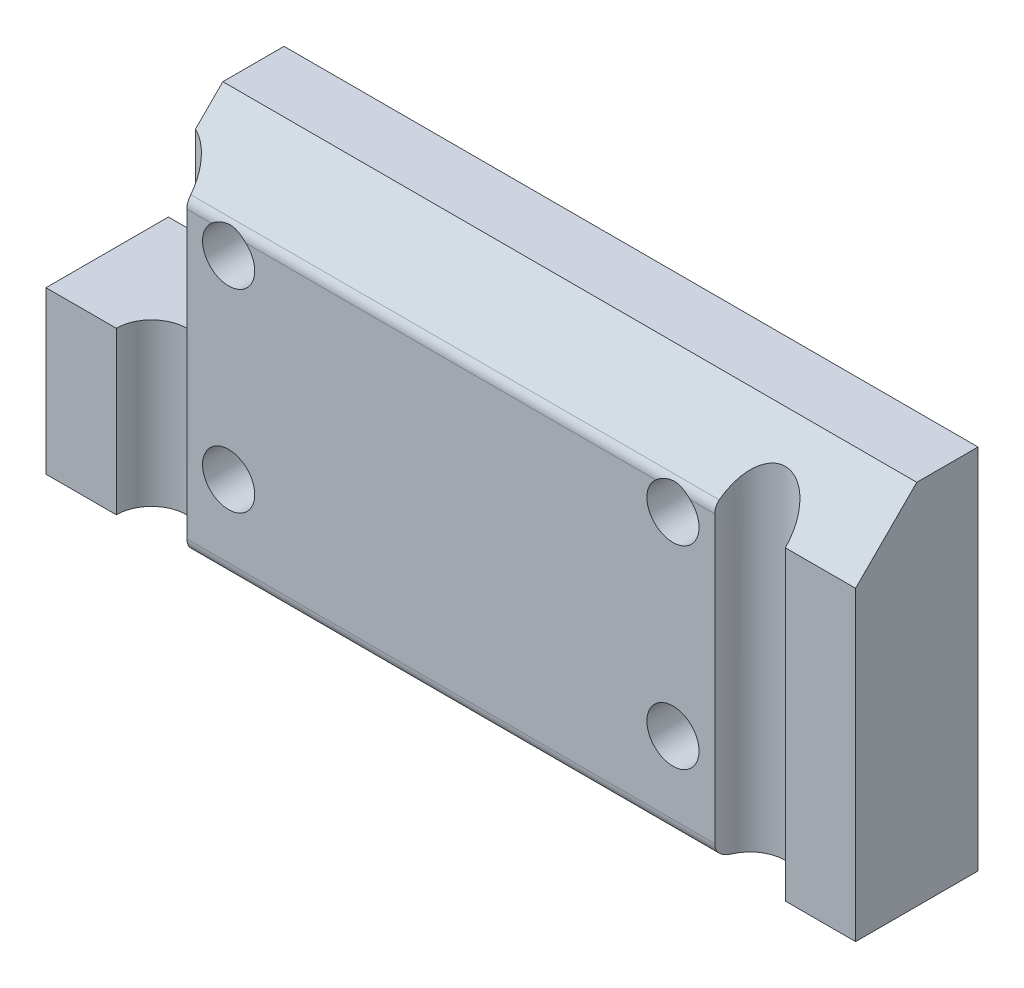
SolidWorks part; units mm, degrees
material "6061-T6 (SS)"
ref_plane "Front" through (0, 0, 0) normal (0, 0, 1) x (1, 0, 0)
ref_plane "Top" through (0, 0, 0) normal (0, 1, 0) x (1, 0, 0)
ref_plane "Right" through (0, 0, 0) normal (1, 0, 0) x (0, 0, -1)
ref_axis "side-side" through (80.9, 0, 0) along (-1, 0, 0)
ref_axis "up-down" through (0, 50, 0) along (0, -1, 0)
ref_axis "front-back" through (0, 0, -80.9) along (0, 0, 1)
sketch "Sketch1" plane through (0, 0, 0) normal (1, 0, 0) x (0, 0, -1)
  line L0 (0, 6.35) -> (3.175, 9.525)
  line L1 (3.175, 9.525) -> (6.35, 9.525)
  line L2 (0, 6.35) -> (0, -9.525)
  line L3 (0, -9.525) -> (6.35, -9.525)
  line L4 (6.35, 9.525) -> (6.35, -9.525)
  point P0 (6.35, 0)
  dimension "D1" = 6.35
  dimension "D2" = 19.05
  dimension "D3" = 45
  dimension "D4" = 3.175
extrude "Boss-Extrude1" add sketch "Sketch1" along normal mid plane 42
hole_wizard "#6-32 Tapped Hole1" positions "Sketch3" profile "Sketch5" tap size "#6-32" standard "ANSI Inch"
sketch "Sketch3" plane through (0, 0, -6.35) normal (0, 0, -1) x (-1, 0, 0)
  line L0 (-9.525, 9.525) -> (-9.525, -9.525) construction
  line L1 (-21, 9.525) -> (21, 9.525) construction
  line L2 (-21, -9.525) -> (21, -9.525) construction
  line L3 (0, 0) -> (0, 16.0303) construction
  point P7 (-11.525, 5.025)
  point P9 (-11.525, -5.025)
  point P11 (11.525, 5.025)
  point P13 (11.525, -5.025)
  dimension "D1" = 9.525
  dimension "D2" = 4.5
  dimension "D3" = 4.5
  dimension "D4" = 2
  dimension "D5" = 23.05
sketch "Sketch5" plane through (-11.525, -5.025, -6.35) normal (1, 0, 0) x (0, 1, 0)
  line L0 (0, 0) -> (0, 10.2107)
  line L1 (0, 10.2107) -> (1.3525, 9.398)
  line L2 (1.3525, 9.398) -> (1.3525, 0)
  line L5 (1.3525, 0) -> (0, 0)
  line L10 (0, 10.2107) -> (-1.3526, 9.398) construction
  line L11 (0, -6.35) -> (0, 107.95) construction
  dimension "Tap Drill Dia." = 2.7051
  dimension "Tap Drill Depth" = 9.398
  dimension "Drill Angle" = 118
hole_wizard "#6 Clearance Hole1" positions "Sketch6" profile "Sketch7" hole size "#6" standard "ANSI Inch" end condition through all
sketch "Sketch6" plane through (0, -9.525, 0) normal (0, -1, 0) x (-1, 0, 0)
  line L0 (-21, 0) -> (21, 0) construction
  line L2 (0, 0) -> (0, 28.1383) construction
  point P0 (-15.525, 0)
  point P7 (15.525, 0)
  dimension "D1" = 31.05
sketch "Sketch7" plane through (15.525, -9.525, 0) normal (1, 0, 0) x (0, 0, -1)
  line L0 (0, 0) -> (0, 19.05)
  line L1 (0, 19.05) -> (1.8288, 19.05)
  line L2 (1.8288, 19.05) -> (1.8288, 0)
  line L5 (1.8288, 0) -> (0, 0)
  line L11 (0, -6.35) -> (0, 107.95) construction
  dimension "Thru Hole Dia." = 3.6576
  dimension "Thru Hole Depth" = 19.05
fillet "Fillet1" radius 0.75 2 edges at (0, -9.525, 0) (0, 6.35, 0)
sketch "Sketch8" plane through (0, 0, 0) normal (0, 0, 1) x (1, 0, 0)
  line L1 (-21, 9.525) -> (-15, 9.525)
  line L2 (-21, 9.525) -> (-21, -1.143)
  line L3 (-21, -1.143) -> (-15, -1.143)
  line L4 (-15, 9.525) -> (-15, -1.143)
  dimension "D1" = 10.668
  dimension "D2" = 6
extrude "Cut-Extrude1" cut sketch "Sketch8" against normal through all
